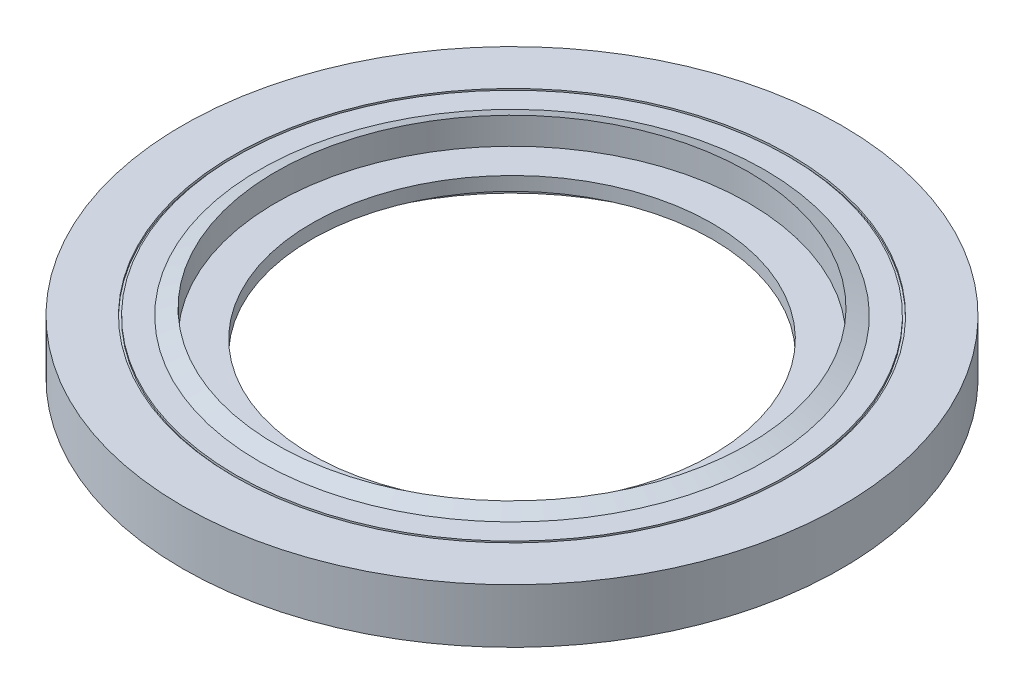
SolidWorks part; units mm, degrees
ref_plane "Front Plane" through (0, 0, 0) normal (0, 0, 1) x (1, 0, 0)
ref_plane "Top Plane" through (0, 0, 0) normal (0, 1, 0) x (1, 0, 0)
ref_plane "Right Plane" through (0, 0, 0) normal (1, 0, 0) x (0, 0, -1)
sketch "Sketch1" plane through (0, 0, 0) normal (0, 0, 1) x (1, 0, 0)
  line L0 (0, 0) -> (0, 5.1453) construction
  line L1 (9.12, -0.3125) -> (9.12, 0.3125)
  line L2 (9.12, -0.3125) -> (11.5, -1.235) construction
  line L3 (11.5, -1.235) -> (12.5667, -1.235)
  line L4 (12.6667, -1.235) -> (15, -1.235)
  line L5 (15, -1.235) -> (15, 1.235)
  line L6 (15, 1.235) -> (12.6667, 1.235)
  line L7 (16.6173, 0) -> (-12.4517, 0) construction
  line L8 (11.5, 1.235) -> (12.5667, 1.235)
  line L9 (9.12, 0.3125) -> (11.5, 1.235) construction
  line L10 (12.6667, 1.235) -> (12.6667, 1.135)
  line L11 (12.6667, 1.135) -> (12.5667, 1.135)
  line L12 (12.5667, 1.135) -> (12.5667, 1.235)
  line L13 (12.5667, -1.135) -> (12.5667, -1.235)
  line L14 (12.6667, -1.135) -> (12.5667, -1.135)
  line L15 (12.6667, -1.235) -> (12.6667, -1.135)
  line L16 (11.5, 1.235) -> (10.75, 1.535)
  line L17 (10.75, 1.535) -> (10.75, 0.3125)
  line L18 (9.12, 0.3125) -> (10.75, 0.3125)
  line L19 (9.12, -0.3125) -> (10.75, -0.3125)
  line L20 (10.75, -1.535) -> (10.75, -0.3125)
  line L21 (11.5, -1.235) -> (10.75, -1.535)
  point P15 (9.12, 0)
  dimension "OD" = 30
  dimension "C" = 18.24
  dimension "d1" = 23
  dimension "S" = 2.47
  dimension "E" = 0.625
  dimension "D2" = 0.1
  dimension "D3" = 0.1
  dimension "D4" = 25.3333
  dimension "P" = 0.3
  dimension "d" = 21.5
revolve "Revolve1" add sketch "Sketch1" angle 360 about L0
ref_axis "Axis1" through (0, 1.6885, 0) along (0, -1, 0)
sketch "Sketch2" plane through (0, 0, 0) normal (0, 0, 1) x (1, 0, 0)
  line L0 (0, 0) -> (0, -4.6258) construction
  line L1 (12.6667, 1.235) -> (15, 1.235)
  line L2 (12.6667, 1.235) -> (12.6667, -1.235)
  line L3 (12.6667, -1.235) -> (15, -1.235)
  line L4 (15, 1.235) -> (15, -1.235)
  line L5 (0, 1.6885) -> (0, -1.6885) construction
revolve "Revolve2" [suppressed] add sketch "Sketch2" angle 360 about L0
equation "\"D4@Sketch1\"=\"d1@Sketch1\" + ( \"OD@Sketch1\" - \"d1@Sketch1\" ) / 3"
